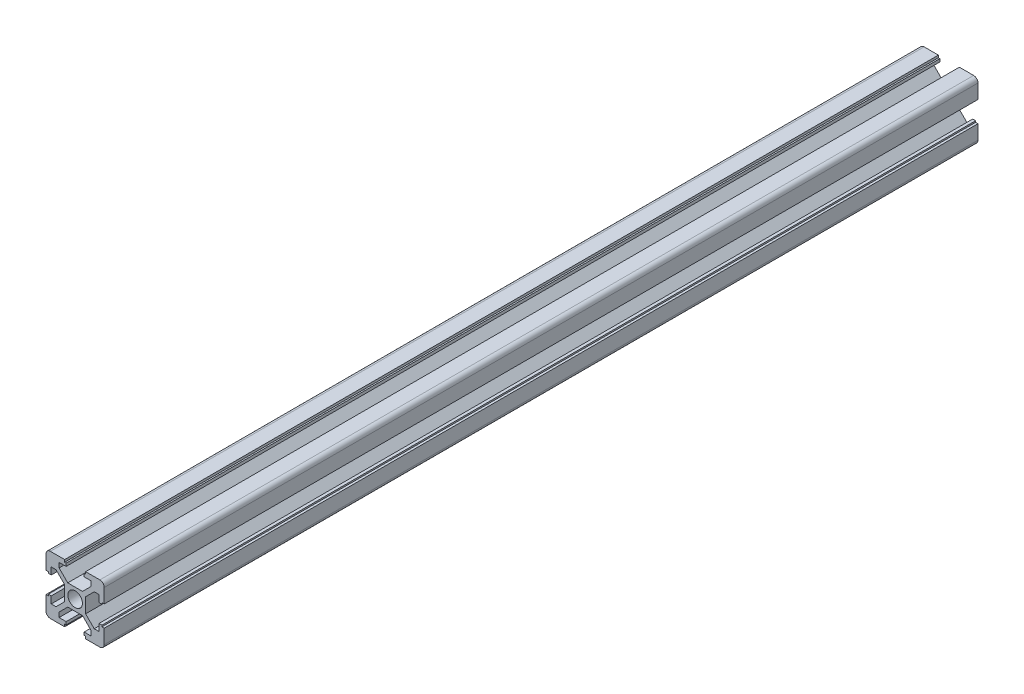
SolidWorks part; units mm, degrees
ref_plane "前视基准面" through (0, 0, 0) normal (0, 0, 1) x (1, 0, 0)
ref_plane "上视基准面" through (0, 0, 0) normal (0, 1, 0) x (1, 0, 0)
ref_plane "右视基准面" through (0, 0, 0) normal (1, 0, 0) x (0, 0, -1)
other "Configuration Table"
sketch "草图1" plane through (0, 0, 0) normal (0, 0, 1) x (1, 0, 0)
  line L0 (-4.4156, 1.3346) -> (-4.4156, 4.4346) construction
  line L1 (-4.4156, 3.874) -> (-4.4156, -1.2047)
  line L2 (1.7237, 4.9346) -> (-3.3549, 4.9346)
  line L3 (2.7844, -1.2047) -> (2.7844, 3.874)
  line L4 (-3.3549, -2.2654) -> (1.7237, -2.2654)
  line L5 (-10.8156, 1.3346) -> (9.1844, 1.3346) construction
  line L6 (-0.8156, 11.3346) -> (-0.8156, -8.6654) construction
  line L7 (-10.8156, 11.3346) -> (-0.8156, 1.3346) construction
  line L8 (-10.8156, 4.9346) -> (-4.4156, 4.9346) construction
  line L9 (-10.0156, 4.4346) -> (-3.9156, 4.4346) construction
  line L10 (-9.0156, 6.8346) -> (-6.3156, 6.8346) construction
  line L11 (-7.3763, 6.8346) -> (-4.4156, 3.874) construction
  line L12 (-10.8156, 9.8346) -> (-10.8156, 4.9346)
  line L13 (-10.8156, 4.9346) -> (-10.0156, 4.9346)
  line L14 (-10.0156, 4.9346) -> (-10.0156, 4.4346)
  line L15 (-10.0156, 4.4346) -> (-9.0156, 4.4346)
  line L16 (-9.0156, 4.4346) -> (-9.0156, 6.8346)
  line L17 (-9.0156, 6.8346) -> (-7.3763, 6.8346)
  line L18 (-7.3763, 6.8346) -> (-4.4156, 3.874)
  line L19 (-3.9156, 10.5346) -> (-3.9156, 9.5346)
  line L20 (-4.4156, 10.5346) -> (-3.9156, 10.5346)
  line L21 (-4.4156, 11.3346) -> (-4.4156, 10.5346)
  line L22 (-9.3156, 11.3346) -> (-4.4156, 11.3346)
  line L23 (-3.9156, 9.5346) -> (-6.3156, 9.5346)
  line L24 (-6.3156, 9.5346) -> (-6.3156, 7.8953)
  line L25 (-6.3156, 7.8953) -> (-3.3549, 4.9346)
  line L26 (9.1844, 11.3346) -> (-0.8156, 1.3346) construction
  line L27 (4.6844, 7.8953) -> (1.7237, 4.9346)
  line L28 (4.6844, 9.5346) -> (4.6844, 7.8953)
  line L29 (2.2844, 9.5346) -> (4.6844, 9.5346)
  line L30 (2.2844, 10.5346) -> (2.2844, 9.5346)
  line L31 (2.7844, 10.5346) -> (2.2844, 10.5346)
  line L32 (2.7844, 11.3346) -> (2.7844, 10.5346)
  line L33 (7.6844, 11.3346) -> (2.7844, 11.3346)
  line L34 (9.1844, 9.8346) -> (9.1844, 4.9346)
  line L35 (9.1844, 4.9346) -> (8.3844, 4.9346)
  line L36 (8.3844, 4.9346) -> (8.3844, 4.4346)
  line L37 (8.3844, 4.4346) -> (7.3844, 4.4346)
  line L38 (7.3844, 4.4346) -> (7.3844, 6.8346)
  line L39 (7.3844, 6.8346) -> (5.7451, 6.8346)
  line L40 (5.7451, 6.8346) -> (2.7844, 3.874)
  line L41 (9.1844, -8.6654) -> (-0.8156, 1.3346) construction
  line L42 (5.7451, -4.1654) -> (2.7844, -1.2047)
  line L43 (7.3844, -4.1654) -> (5.7451, -4.1654)
  line L44 (7.3844, -1.7654) -> (7.3844, -4.1654)
  line L45 (8.3844, -1.7654) -> (7.3844, -1.7654)
  line L46 (8.3844, -2.2654) -> (8.3844, -1.7654)
  line L47 (9.1844, -2.2654) -> (8.3844, -2.2654)
  line L48 (9.1844, -7.1654) -> (9.1844, -2.2654)
  line L49 (7.6844, -8.6654) -> (2.7844, -8.6654)
  line L50 (2.7844, -8.6654) -> (2.7844, -7.8654)
  line L51 (2.7844, -7.8654) -> (2.2844, -7.8654)
  line L52 (2.2844, -7.8654) -> (2.2844, -6.8654)
  line L53 (2.2844, -6.8654) -> (4.6844, -6.8654)
  line L54 (4.6844, -6.8654) -> (4.6844, -5.226)
  line L55 (4.6844, -5.226) -> (1.7237, -2.2654)
  line L56 (-10.8156, -8.6654) -> (-0.8156, 1.3346) construction
  line L57 (-6.3156, -5.226) -> (-3.3549, -2.2654)
  line L58 (-6.3156, -6.8654) -> (-6.3156, -5.226)
  line L59 (-3.9156, -6.8654) -> (-6.3156, -6.8654)
  line L60 (-3.9156, -7.8654) -> (-3.9156, -6.8654)
  line L61 (-4.4156, -7.8654) -> (-3.9156, -7.8654)
  line L62 (-4.4156, -8.6654) -> (-4.4156, -7.8654)
  line L63 (-9.3156, -8.6654) -> (-4.4156, -8.6654)
  line L64 (-10.8156, -7.1654) -> (-10.8156, -2.2654)
  line L65 (-10.8156, -2.2654) -> (-10.0156, -2.2654)
  line L66 (-10.0156, -2.2654) -> (-10.0156, -1.7654)
  line L67 (-10.0156, -1.7654) -> (-9.0156, -1.7654)
  line L68 (-9.0156, -1.7654) -> (-9.0156, -4.1654)
  line L69 (-9.0156, -4.1654) -> (-7.3763, -4.1654)
  line L70 (-7.3763, -4.1654) -> (-4.4156, -1.2047)
  arc A0 (-10.8156, 9.8346) -> (-9.3156, 11.3346) centre (-9.3156, 9.8346) cw
  circle A1 centre (-0.8156, 1.3346) radius 2.5
  arc A2 (7.6844, 11.3346) -> (9.1844, 9.8346) centre (7.6844, 9.8346) cw
  arc A3 (9.1844, -7.1654) -> (7.6844, -8.6654) centre (7.6844, -7.1654) cw
  arc A4 (-9.3156, -8.6654) -> (-10.8156, -7.1654) centre (-9.3156, -7.1654) cw
  point P13 (-0.8156, 1.3346)
  point P84 (-0.8156, 1.3346)
  dimension "D8" = 1.5
  dimension "D9" = 5
  dimension "D1" = 20
  dimension "D2" = 6.2
  dimension "D3" = 7.2
  dimension "D4" = 11
  dimension "D5" = 1.5
  dimension "D6" = 0.8
  dimension "D7" = 1.8
  dimension "D10" = 7.2
extrude "凸台-拉伸1" add sketch "草图1" along normal blind 300 contours A1 | L34 L35 L36 L37 L38 L39 L40 L3 L42 L43 L44 L45 L46 L47 L48 A3 L49 L50 L51 L52 L53 L54 L55 L4 L57 L58 L59 L60 L61 L62 L63 A4 L64 L65 L66 L67 L68 L69 L70 L1 L18 L17 L16 L15 L14 L13 L12 A0 L22 L21 L20 L19 L23 L24 L25 L2 L27 L28 L29 L30 L31 L32 L33 A2 region at (-0.8156, 1.3346, 0)
sketch "草图2" plane through (2.7844, 0, 0) normal (1, 0, 0) x (0, 0, -1)
  circle A0 centre (-250, 1.3346) radius 1.75
  circle A1 centre (-50, 1.3346) radius 1.75
extrude "切除-拉伸1" cut sketch "草图2" against normal blind 39
